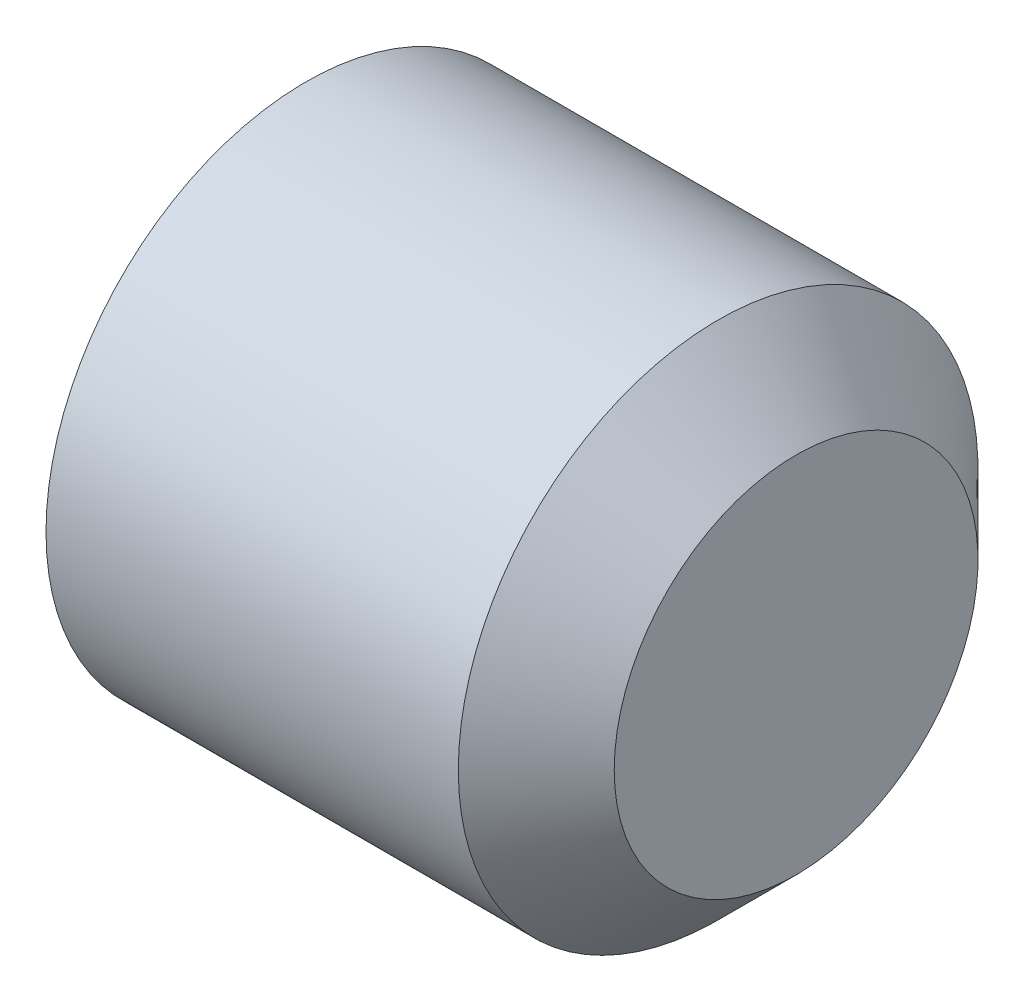
SolidWorks part; units mm, degrees
ref_plane "Front Plane" through (0, 0, 0) normal (0, 0, 1) x (1, 0, 0)
ref_plane "Top Plane" through (0, 0, 0) normal (0, 1, 0) x (1, 0, 0)
ref_plane "Right Plane" through (0, 0, 0) normal (1, 0, 0) x (0, 0, -1)
sketch "Sketch1" plane through (0, 0, 0) normal (0, 0, 1) x (1, 0, 0)
  line L0 (5, 0) -> (5, -1.75)
  line L1 (5, -1.75) -> (4.25, -2.5)
  line L2 (4.25, -2.5) -> (0.2832, -2.5)
  line L3 (0.2832, -2.5) -> (0, -2.0095)
  line L4 (0, -2.0095) -> (0, -1.4434)
  line L5 (0, -1.4434) -> (0.8333, 0)
  line L6 (0.8333, 0) -> (5, 0)
  line L7 (0.8333, 0) -> (5, 0) construction
revolve "Revolve1" add sketch "Sketch1" angle 360 about L7
cosmetic thread "Cosmetic Thread1" parameters "D1"=5, "D2"=4.019
sketch "Sketch2" plane through (0, 0, 0) normal (1, 0, 0) x (0, 0, -1)
  line L0 (-1.4434, 0) -> (-0.7217, -1.25)
  line L1 (-0.7217, -1.25) -> (0.7217, -1.25)
  line L2 (0.7217, -1.25) -> (1.4434, 0)
  line L3 (1.4434, 0) -> (0.7217, 1.25)
  line L4 (0.7217, 1.25) -> (-0.7217, 1.25)
  line L5 (-0.7217, 1.25) -> (-1.4434, 0)
extrude "Cut-Extrude1" cut sketch "Sketch2" along normal blind 2
ref_plane "Plane1" through (5, 0, 0) normal (1, 0, 0) x (0, 0, -1)
ref_plane "IP1 XY" through (0, 0, 0) normal (1, 0, 0) x (0, 0, -1)
ref_plane "IP1 XZ" through (0, 0, 0) normal (0, -1, 0) x (-1, 0, 0)
ref_plane "IP1 YZ" through (0, 0, 0) normal (0, 0, -1) x (-1, 0, 0)
ref_axis "IP1 X" through (0, 0, 80.9) along (0, 0, -1)
ref_axis "IP1 Y" through (0, -50, 0) along (0, 1, 0)
ref_axis "IP1 Z" through (80.9, 0, 0) along (-1, 0, 0)
sketch3d "IP1"
  point P0 (0, 0, 0)
ref_plane "IP2 XY" through (5, 0, 0) normal (1, 0, 0) x (0, 0, -1)
ref_plane "IP2 XZ" through (0, 0, 0) normal (0, -1, 0) x (-1, 0, 0)
ref_plane "IP2 YZ" through (0, 0, 0) normal (0, 0, -1) x (-1, 0, 0)
ref_axis "IP2 X" through (5, 0, 80.9) along (0, 0, -1)
ref_axis "IP2 Y" through (5, -50, 0) along (0, 1, 0)
ref_axis "IP2 Z" through (80.9, 0, 0) along (-1, 0, 0)
sketch3d "IP2"
  point P0 (5, 0, 0)
other "Freeze***"
